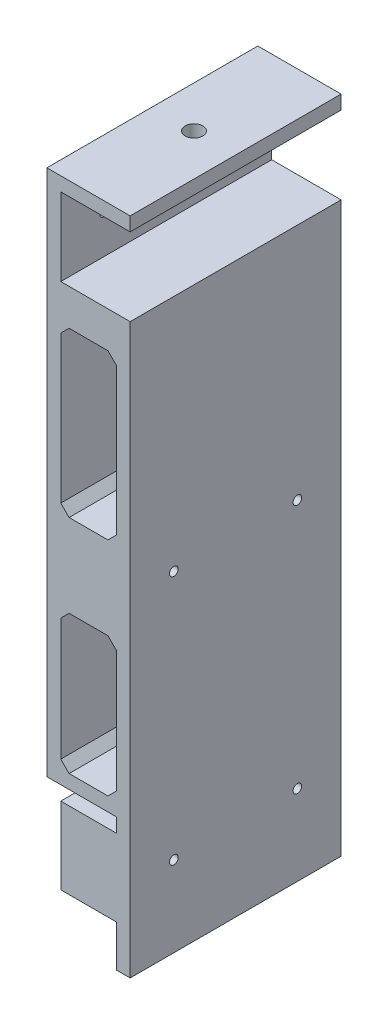
SolidWorks part; units mm, degrees
ref_plane "前视基准面" through (0, 0, 0) normal (0, 0, 1) x (1, 0, 0)
ref_plane "上视基准面" through (0, 0, 0) normal (0, 1, 0) x (1, 0, 0)
ref_plane "右视基准面" through (0, 0, 0) normal (1, 0, 0) x (0, 0, -1)
other "Configuration Table"
sketch "草图1" plane through (0, 0, 0) normal (0, 0, 1) x (1, 0, 0)
  line L0 (12.5, -13.85) -> (12.5, -28.85)
  line L1 (-12.5, 13.85) -> (7.5064, 13.85)
  line L2 (-12.5, 13.85) -> (-12.5, -13.85)
  line L3 (-12.5, -13.85) -> (7.5064, -13.85)
  line L4 (12.5, 13.85) -> (12.5, -13.85)
  line L5 (-12.5, 13.85) -> (12.5, -13.85) construction
  line L6 (-12.5, -13.85) -> (12.5, 13.85) construction
  line L7 (12.5, -28.85) -> (7.5064, -28.85)
  line L8 (7.5064, -28.85) -> (7.5064, -13.85)
  line L9 (7.5064, -13.85) -> (7.5064, 13.85) construction
  line L10 (7.5064, 18.95) -> (-17.4936, 18.95)
  line L12 (7.5064, 13.85) -> (7.5064, 18.95)
  line L14 (12.5, 13.85) -> (12.5, 18.95)
  line L15 (-17.4936, 18.95) -> (-17.4936, 208.95)
  line L16 (-17.4936, 208.95) -> (12.5, 208.95)
  line L17 (12.5, 208.95) -> (12.5, 203.95)
  line L18 (12.5, 203.95) -> (-12.4936, 203.95)
  line L19 (-12.4936, 203.95) -> (-12.4936, 175.95)
  line L20 (-12.4936, 175.95) -> (12.5, 175.95)
  line L21 (12.5, 175.95) -> (12.5, 18.95)
  point P0 (0, 0)
  dimension "D1" = 27.7
  dimension "D2" = 25
  dimension "D3" = 4.9936
  dimension "D4" = 15
  dimension "D5" = 5.1
  dimension "D6" = 25
  dimension "D7" = 190
  dimension "D8" = 5
  dimension "D9" = 5
  dimension "D10" = 28
extrude "凸台-拉伸1" add sketch "草图1" along normal blind 76
sketch "草图2" plane through (-12.4936, 0, 0) normal (1, 0, 0) x (0, 0, -1)
  line L0 (-76, 189.95) -> (0, 189.95) construction
  line L1 (-76, 175.95) -> (-76, 203.95) construction
  line L2 (0, 175.95) -> (0, 203.95) construction
  circle A0 centre (-60.4, 189.95) radius 1.57
  circle A1 centre (-15.6, 189.95) radius 1.57
  point P10 (-38, 189.95)
  dimension "D1" = 22.4
  dimension "D2" = 22.4
extrude "切除-拉伸1" cut sketch "草图2" against normal up to next
sketch "草图3" plane through (-12.5, 0, 0) normal (-1, 0, 0) x (0, 0, 1)
  line L0 (0, 0.15) -> (76, 0.15) construction
  line L1 (15.75, 0.15) -> (15.75, 90.15) construction
  line L2 (15.75, 90.15) -> (60.25, 90.15) construction
  line L3 (0, 13.85) -> (0, -13.85) construction
  line L4 (76, 13.85) -> (76, -13.85) construction
  line L5 (76, -13.85) -> (0, -13.85) construction
  line L6 (60.25, 90.15) -> (60.25, 0.15) construction
  circle A0 centre (15.75, 0.15) radius 1.57
  circle A1 centre (60.25, 0.15) radius 1.57
  point P12 (38, 0.15)
  point P15 (0, 0)
  dimension "D2" = 22.25
  dimension "D1" = 14
  dimension "D3" = 22.25
  dimension "D4" = 90
extrude "切除-拉伸2" cut sketch "草图3" against normal up to next
sketch "草图4" plane through (0, 208.95, 0) normal (0, 1, 0) x (1, 0, 0)
  line L0 (-17.4936, -38) -> (12.5, -38) construction
  line L1 (-17.4936, -76) -> (-17.4936, 0) construction
  line L2 (12.5, -76) -> (12.5, 0) construction
  circle A0 centre (-2.4968, -38) radius 3.17
extrude "切除-拉伸3" cut sketch "草图4" against normal up to next
sketch "草图5" plane through (-12.5, 0, 0) normal (-1, 0, 0) x (0, 0, 1)
sketch "草图6" plane through (-17.4936, 0, 0) normal (-1, 0, 0) x (0, 0, 1)
  line L0 (15.75, 0.15) -> (15.75, 90.15) construction
  line L1 (60.25, 0.15) -> (60.25, 90.15) construction
  circle A0 centre (15.75, 90.15) radius 1.57
  circle A1 centre (60.25, 90.15) radius 1.57
  dimension "D1" = 90
extrude "切除-拉伸4" cut sketch "草图6" against normal up to next
sketch "草图7" plane through (0, 0, 76) normal (0, 0, 1) x (1, 0, 0)
  line L0 (12.5, -28.85) -> (12.5, 175.95) construction
  line L1 (-12.4936, 73.95) -> (7.5, 73.95)
  line L2 (-12.4936, 73.95) -> (-12.4936, 23.95)
  line L3 (-12.4936, 23.95) -> (7.5, 23.95)
  line L4 (7.5, 73.95) -> (7.5, 23.95)
  line L5 (-12.4936, 162.872) -> (7.5, 162.872)
  line L6 (-12.4936, 162.872) -> (-12.4936, 103.8364)
  line L7 (-12.4936, 103.8364) -> (7.5, 103.8364)
  line L8 (7.5, 162.872) -> (7.5, 103.8364)
  line L9 (-17.4936, 208.95) -> (-17.4936, 18.95) construction
  line L10 (-17.4936, 18.95) -> (7.5064, 18.95) construction
  point P8 (3.9738, 103.8364)
  dimension "D1" = 5
  dimension "D2" = 5
  dimension "D3" = 5
  dimension "D4" = 5
  dimension "D5" = 5
  dimension "D6" = 55
extrude "切除-拉伸5" cut sketch "草图7" against normal up to next
fillet "倒角1" radius 3 1 edges at (-12.4936, 162.872, 38) type face fillet profile chamfer first side face at (-12.4936, 133.3542, 38) second side face at (-2.4968, 162.872, 38)
fillet "倒角2" radius 3 1 edges at (7.5, 103.8364, 38) type face fillet profile chamfer first side face at (7.5, 133.3542, 38) second side face at (-2.4968, 103.8364, 38)
fillet "倒角3" radius 3 1 edges at (-12.4936, 73.95, 38) type face fillet profile chamfer first side face at (-2.4968, 73.95, 38) second side face at (-12.4936, 48.95, 38)
fillet "倒角4" radius 3 1 edges at (7.5, 23.95, 38) type face fillet profile chamfer first side face at (7.5, 48.95, 38) second side face at (-2.4968, 23.95, 38)
fillet "倒角5" radius 3 1 edges at (-12.4936, 23.95, 38) type face fillet profile chamfer first side face at (-12.4936, 47.45, 38) second side face at (-3.9968, 23.95, 38)
fillet "倒角6" radius 3 1 edges at (7.5, 73.95, 38) type face fillet profile chamfer first side face at (-0.9968, 73.95, 38) second side face at (7.5, 50.45, 38)
fillet "倒角7" radius 3 1 edges at (7.5, 162.872, 38) type face fillet profile chamfer first side face at (-0.9968, 162.872, 38) second side face at (7.5, 134.8542, 38)
fillet "倒角8" radius 3 1 edges at (-12.4936, 103.8364, 38) type face fillet profile chamfer first side face at (-12.4936, 131.8542, 38) second side face at (-3.9968, 103.8364, 38)
